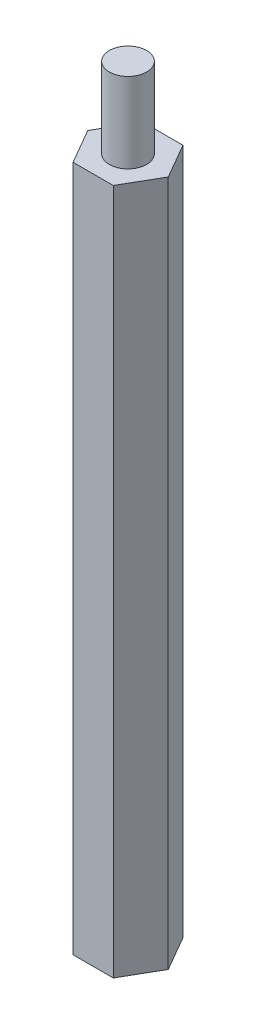
SolidWorks part; units mm, degrees
ref_plane "Front Plane" through (0, 0, 0) normal (0, 0, 1) x (1, 0, 0)
ref_plane "Top Plane" through (0, 0, 0) normal (0, 1, 0) x (1, 0, 0)
ref_plane "Right Plane" through (0, 0, 0) normal (1, 0, 0) x (0, 0, -1)
sketch "Sketch1" plane through (0, 0, 0) normal (0, 1, 0) x (1, 0, 0)
  line L1 (2.9329, 0) -> (1.4665, 2.54)
  line L2 (1.4665, 2.54) -> (-1.4665, 2.54)
  line L3 (-1.4665, 2.54) -> (-2.9329, 0)
  line L4 (-2.9329, 0) -> (-1.4665, -2.54)
  line L5 (-1.4665, -2.54) -> (1.4665, -2.54)
  line L6 (1.4665, -2.54) -> (2.9329, 0)
  circle A0 centre (0, 0) radius 2.54 construction
  dimension "D1" = 5.08
extrude "Boss-Extrude1" add sketch "Sketch1" along normal blind 50.038
sketch "Sketch2" plane through (0, 50.038, 0) normal (0, 1, 0) x (1, 0, 0)
  line L0 (0, 2.54) -> (0, -2.54) construction
  line L1 (-1.4665, -2.54) -> (1.4665, -2.54) construction
  line L2 (1.4665, 2.54) -> (-1.4665, 2.54) construction
  circle A0 centre (0, 0) radius 1.3589
  dimension "D1" = 2.7178
extrude "Boss-Extrude2" add sketch "Sketch2" along normal blind 5.842
sketch "Sketch3" plane through (0, 0, 0) normal (0, -1, 0) x (-1, 0, 0)
  line L0 (-2.1997, -1.27) -> (2.1997, 1.27) construction
  line L1 (1.4665, 2.54) -> (2.9329, 0) construction
  line L2 (-1.4665, -2.54) -> (-2.9329, 0) construction
  line L3 (-1.4665, 2.54) -> (1.4665, -2.54) construction
  circle A0 centre (0, 0) radius 1.3589
  point P20 (-2.9329, 0)
  dimension "D1" = 2.7178
extrude "Cut-Extrude1" cut sketch "Sketch3" against normal blind 8.382
